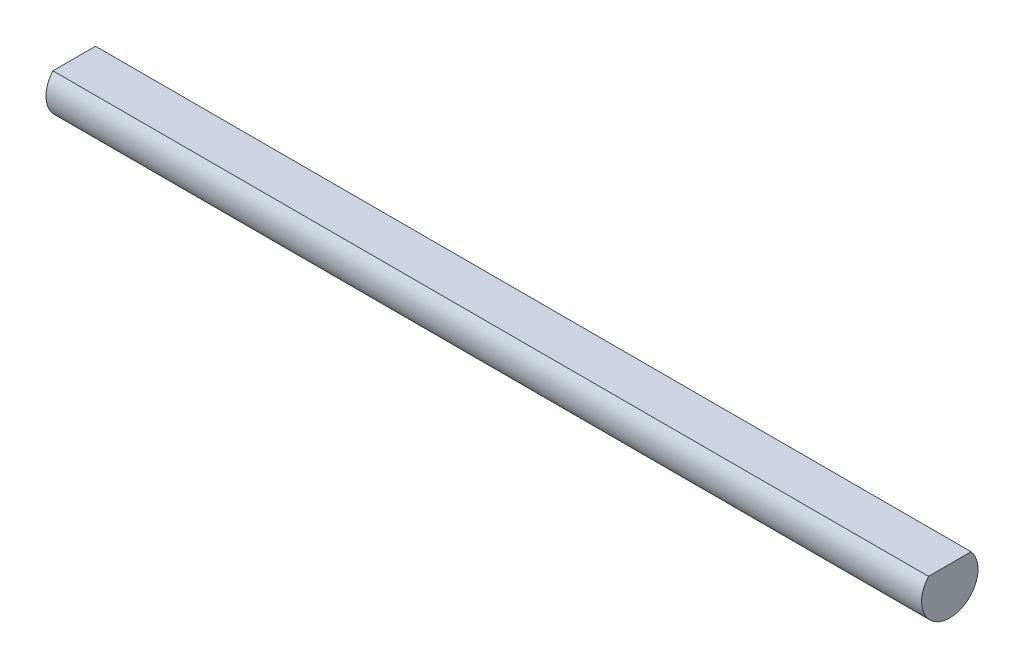
SolidWorks part; units mm, degrees
ref_plane "Front Plane" through (0, 0, 0) normal (0, 0, 1) x (1, 0, 0)
ref_plane "Top Plane" through (0, 0, 0) normal (0, 1, 0) x (1, 0, 0)
ref_plane "Right Plane" through (0, 0, 0) normal (1, 0, 0) x (0, 0, -1)
sketch "Sketch1" plane through (0, 0, 0) normal (1, 0, 0) x (0, 0, -1)
  line L0 (0, -1.5) -> (0, 1)
  line L1 (0, 1) -> (-1.118, 1)
  line L2 (-1.118, 1) -> (1.118, 1)
  line L3 (-1.0954, 0.95) -> (1.0954, 0.95)
  arc A0 (-1.118, 1) -> (1.118, 1) centre (0, 0) ccw
  arc A1 (-1.0954, 0.95) -> (1.0954, 0.95) centre (0, 0) ccw
  dimension "D1" = 3
  dimension "D2" = 2.5
  dimension "D3" = 0.05
extrude "Boss-Extrude1" add sketch "Sketch1" along normal blind 22.5 and the other way blind 22.5 contours L3 A1 L0 | L0 A1 L3 region at (0, -0.1499, 0.6405) region at (0, -0.1499, -0.6405)
